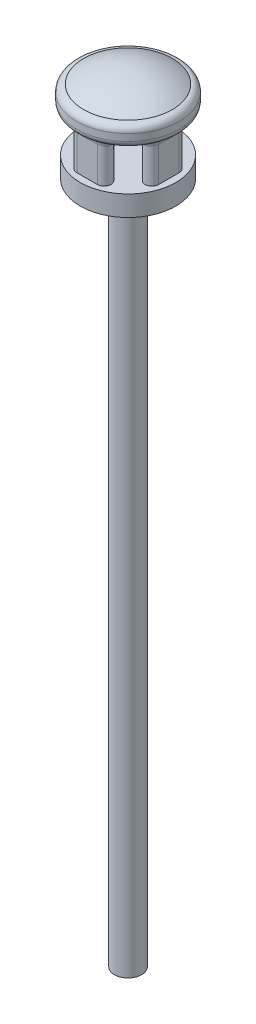
SolidWorks part; units mm, degrees
ref_plane "Front Plane" through (0, 0, 0) normal (0, 0, 1) x (1, 0, 0)
ref_plane "Top Plane" through (0, 0, 0) normal (0, 1, 0) x (1, 0, 0)
ref_plane "Right Plane" through (0, 0, 0) normal (1, 0, 0) x (0, 0, -1)
sketch "Sketch1" plane through (0, 0, 0) normal (0, 1, 0) x (1, 0, 0)
  circle A0 centre (0, 0) radius 9.525
  dimension "D1" = 19.05
extrude "button top" add sketch "Sketch1" along normal blind 3.81
sketch "Sketch2" plane through (0, 0, 0) normal (0, -1, 0) x (1, 0, 0)
  line L9 (-1.905, 6.35) -> (1.905, 6.35) construction
  line L10 (-1.905, 7.62) -> (1.905, 7.62)
  line L11 (-1.905, 5.08) -> (1.905, 5.08)
  arc A6 (-1.905, 7.62) -> (-1.905, 5.08) centre (-1.905, 6.35) ccw
  arc A7 (1.905, 5.08) -> (1.905, 7.62) centre (1.905, 6.35) ccw
  point P22 (0, 6.35)
  dimension "D2" = 1.27
  dimension "D1" = 6.35
  dimension "D8" = 3.81
extrude "connecting leg" add sketch "Sketch2" along normal blind 7.62
ref_axis "central axis" through (0, 3.81, 0) along (0, -1, 0)
pattern_circular "moar legs" count 4 over 360 about axis through (0, 3.81, 0) along (0, -1, 0) of "connecting leg"
ref_plane "base plane" through (0, -7.62, 0) normal (0, -1, 0) x (-1, 0, 0)
sketch "Sketch3" plane through (0, -7.62, 0) normal (0, -1, 0) x (-1, 0, 0)
  circle A0 centre (0, 0) radius 8.89
extrude "base" add sketch "Sketch3" along normal blind 3.81 separate body
fillet "round top" radius 1.27 2 edges at (0, 3.81, 9.525) (0, 0, 9.525)
fillet "round bars" radius 1.27 16 edges at (0, 0, 5.08) (-3.175, 0, 6.35) (0, 0, 7.62) (3.175, 0, 6.35) (5.08, 0, 0) (6.35, 0, 3.175) (7.62, 0, 0) (6.35, 0, -3.175) (3.175, 0, -6.35) (0, 0, -7.62) (-3.175, 0, -6.35) (0, 0, -5.08) (-5.08, 0, 0) (-6.35, 0, -3.175) (-7.62, 0, 0) (-6.35, 0, 3.175)
dome "button ness" faces to dome 1 distance 2.54 reverse direction no elliptical dome no face at (0, 3.81, 8.255) parameters "D1"=2.54
ref_point "center of face"
sketch "Sketch6" plane through (0, -11.43, 0) normal (0, -1, 0) x (1, 0, 0)
  circle A0 centre (0, 0) radius 2.54
extrude "flag" add sketch "Sketch6" along normal blind 127
fillet "flag fillet" radius 2.54 1 edges at (0, -11.43, -2.54)
